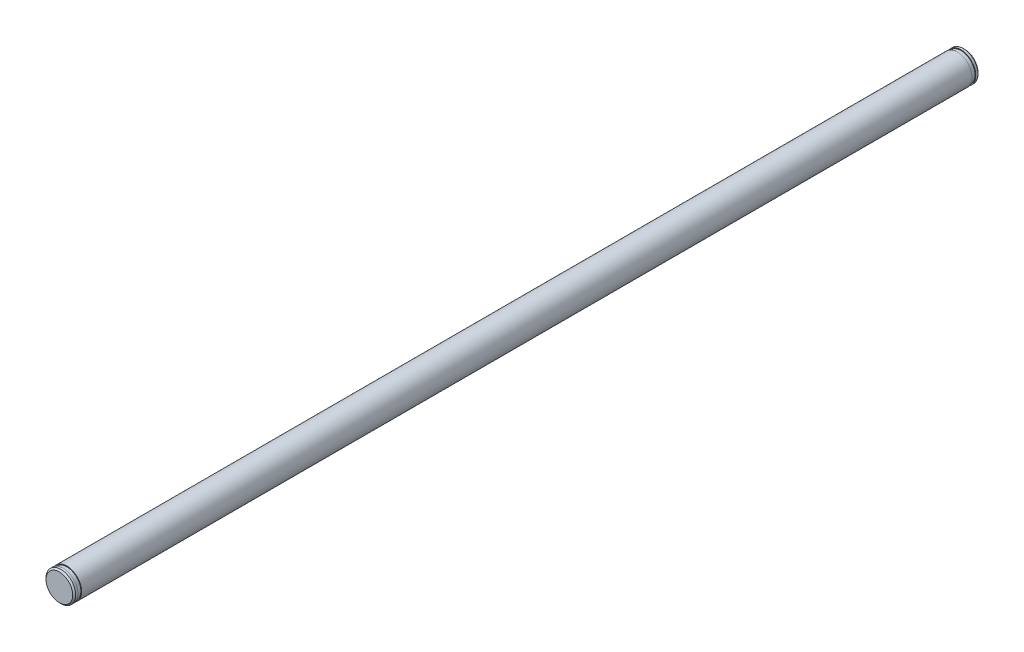
SolidWorks part; units mm, degrees
ref_plane "Vorne" through (0, 0, 0) normal (0, 0, 1) x (1, 0, 0)
ref_plane "Oben" through (0, 0, 0) normal (0, 1, 0) x (1, 0, 0)
ref_plane "Seite" through (0, 0, 0) normal (1, 0, 0) x (0, 0, -1)
sketch "Skizze1" plane through (0, 0, 0) normal (0, 0, 1) x (1, 0, 0)
  circle A0 centre (0, 0) radius 2
  point P3 (0, -3)
  dimension "D1" = 4
  dimension "D2" = 3
extrude "Aufsatz-Linear austragen1" add sketch "Skizze1" along normal mid plane 122
sketch "Skizze2" plane through (0, 0, 61) normal (0, 0, 1) x (1, 0, 0)
  point P0 (0, 0)
sketch "Skizze7" plane through (0, 0, 0) normal (1, 0, 0) x (0, 0, -1)
  line L0 (-60.5, 2) -> (-60.5, 1.9)
  line L1 (61, 2) -> (-61, 2) construction
  line L2 (-60.5, 1.9) -> (-60, 1.9)
  line L3 (-60, 1.9) -> (-60, 2)
  line L4 (-60, 2) -> (-60.5, 2)
  line L5 (60, 2) -> (60, 1.9)
  line L6 (60, 1.9) -> (60.5, 1.9)
  line L7 (60.5, 1.9) -> (60.5, 2)
  line L8 (60.5, 2) -> (60, 2)
  line L9 (-61, 2) -> (-61, -2) construction
  line L10 (61, 0) -> (-61, 0) construction
  line L11 (61, -2) -> (61, 2) construction
  point P16 (0, 0)
  dimension "D1" = 0.1
  dimension "D2" = 0.5
  dimension "D3" = 0.5
  dimension "D4" = 120
revolve "Schnitt-Rotation1" cut sketch "Skizze7" angle 360 about L10
chamfer "Fase1" distance 0.2 angle 45 2 edges at (2, 0, -61) (2, 0, 61)
